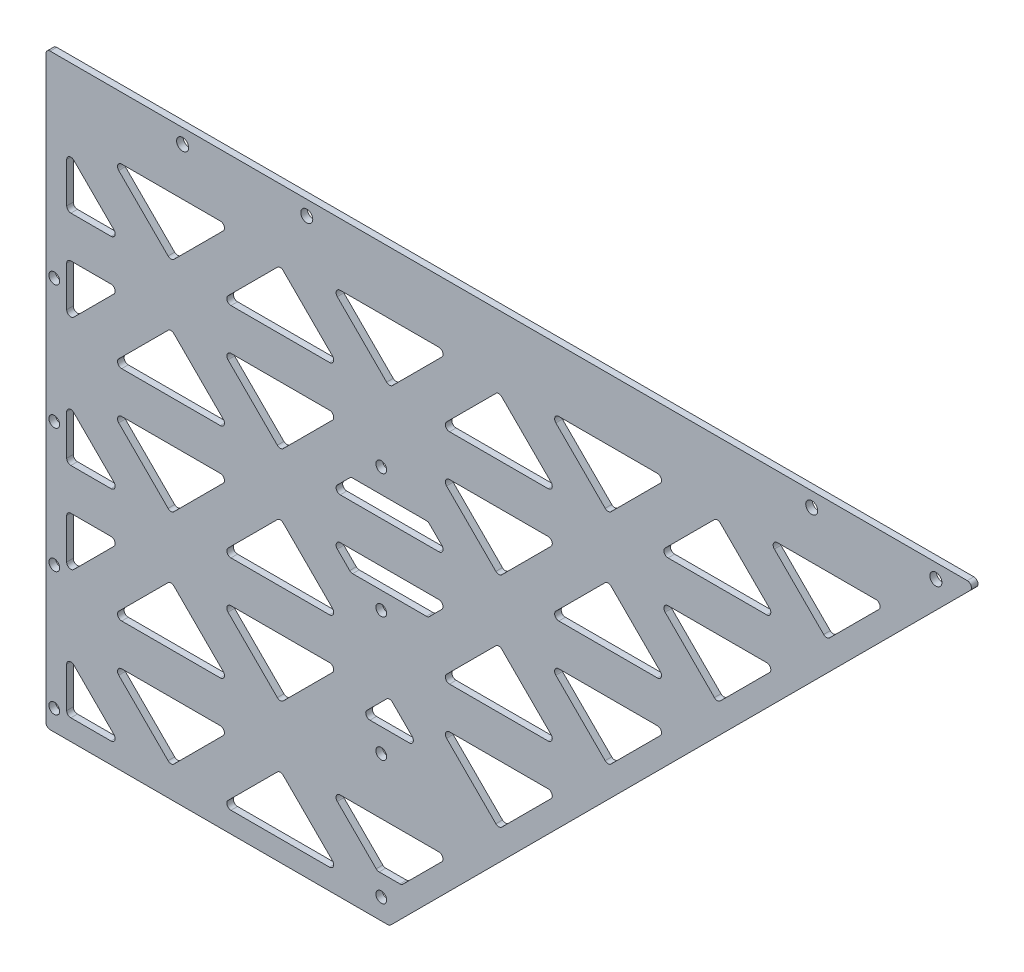
SolidWorks part; units mm, degrees
material "6061-T4 (SS)"
ref_plane "Front Plane" through (0, 0, 0) normal (0, 0, 1) x (1, 0, 0)
ref_plane "Top Plane" through (0, 0, 0) normal (0, 1, 0) x (1, 0, 0)
ref_plane "Right Plane" through (0, 0, 0) normal (1, 0, 0) x (0, 0, -1)
sketch "Sketch1" plane through (0, 0, 0) normal (0, 0, 1) x (1, 0, 0)
  line L0 (0, -71) -> (142, 71)
  line L1 (-83, 71) -> (142, 71)
  line L2 (-83, 71) -> (-83, -71)
  line L3 (-83, -71) -> (0, -71)
  line L6 (-83, 0) -> (71, 0) construction
  line L7 (0, -71) -> (0, 71) construction
  dimension "D1" = 142
  dimension "D2" = 83
  dimension "D3" = 45
extrude "Main Shape" add sketch "Sketch1" along normal mid plane 1.5875
hole_wizard "Body fasteners" positions "Sketch6" profile "Sketch7" hole size "M2" standard "ANSI Metric" end condition through all
sketch "Sketch6" plane through (0, 0, -0.7937) normal (0, 0, -1) x (-1, 0, 0)
  line L0 (81, 71) -> (81, -71) construction
  line L1 (83, 71) -> (-142, 71) construction
  line L2 (83, -71) -> (0, -71) construction
  line L4 (83, 71) -> (83, -71) construction
  line L5 (81, -66) -> (81, -36) construction
  line L6 (41.5, 71) -> (41.5, -71) construction
  line L8 (2, -66) -> (2, -36) construction
  line L9 (2, 71) -> (2, -71) construction
  point P9 (81, -66)
  point P41 (81, -36)
  point P42 (81, -6)
  point P43 (81, 24)
  point P54 (2, 24)
  point P55 (2, -6)
  point P56 (2, -36)
  point P57 (2, -66)
  dimension "D1" = 5
  dimension "D2" = 2
  dimension "D3" = 4
  dimension "D4" = 30
sketch "Sketch7" plane through (-81, -66, -0.7937) normal (1, 0, 0) x (0, 1, 0)
  line L0 (0, 0) -> (0, 1.5875)
  line L1 (0, 1.5875) -> (1.3, 1.5875)
  line L2 (1.3, 1.5875) -> (1.3, 0)
  line L5 (1.3, 0) -> (0, 0)
  line L11 (0, -6.35) -> (0, 107.95) construction
  dimension "Thru Hole Dia." = 2.6
  dimension "Thru Hole Depth" = 1.5875
hole_wizard "M2.5 Clearance Hole1" positions "Sketch11" profile "Sketch12" hole size "M2.5" standard "ANSI Metric" end condition through all
sketch "Sketch11" plane through (0, 0, 0.7937) normal (0, 0, 1) x (1, 0, 0)
  line L0 (132, 67.5) -> (132, 71) construction
  line L1 (-83, 71) -> (142, 71) construction
  line L3 (132, 67.5) -> (138.5, 67.5) construction
  line L4 (0, -71) -> (142, 71) construction
  line L6 (-83, 71) -> (-83, -71) construction
  point P0 (132, 67.5)
  point P17 (-50, 67.5)
  point P28 (-20, 67.5)
  point P31 (102, 67.5)
  dimension "D1" = 3.5
  dimension "D2" = 10
  dimension "D3" = 33
  dimension "D4" = 30
  dimension "D5" = 30
sketch "Sketch12" plane through (132, 67.5, 0.7937) normal (1, 0, 0) x (0, -1, 0)
  line L0 (0, 0) -> (0, 1.5875)
  line L1 (0, 1.5875) -> (1.45, 1.5875)
  line L2 (1.45, 1.5875) -> (1.45, 0)
  line L5 (1.45, 0) -> (0, 0)
  line L11 (0, -6.35) -> (0, 107.95) construction
  dimension "Thru Hole Dia." = 2.9
  dimension "Thru Hole Depth" = 1.5875
sketch "Sketch13" plane through (0, 0, 0.7937) normal (0, 0, 1) x (1, 0, 0)
  line L0 (-83, 61) -> (132, 61)
  line L1 (-83, 71) -> (-83, -71) construction
  line L2 (0, -71) -> (142, 71) construction
  line L3 (-83, 71) -> (142, 71) construction
  line L4 (0, -71) -> (142, 71) construction
  line L5 (0, -71) -> (0, 71) construction
  line L6 (79.2, 61) -> (105.6, 34.6)
  line L7 (105.6, 34.6) -> (52.8, 34.6)
  line L8 (52.8, 34.6) -> (79.2, 61)
  line L9 (52.8, 34.6) -> (26.4, 61)
  line L10 (26.4, 61) -> (0, 34.6)
  line L11 (0, 34.6) -> (52.8, 34.6)
  line L12 (26.4, 53.9289) -> (12.0711, 39.6)
  line L13 (38.4711, 56) -> (52.8, 41.6711)
  line L14 (12.0711, 39.6) -> (40.7289, 39.6)
  line L15 (40.7289, 39.6) -> (26.4, 53.9289)
  line L16 (79.2, 53.9289) -> (64.8711, 39.6)
  line L17 (64.8711, 39.6) -> (93.5289, 39.6)
  line L18 (93.5289, 39.6) -> (79.2, 53.9289)
  line L19 (52.8, 41.6711) -> (67.1289, 56)
  line L20 (67.1289, 56) -> (38.4711, 56)
  line L21 (-67.1289, 56) -> (-52.8, 41.6711)
  line L22 (91.2711, 56) -> (105.6, 41.6711)
  line L23 (105.6, 41.6711) -> (119.9289, 56)
  line L24 (119.9289, 56) -> (91.2711, 56)
  line L25 (0, 34.6) -> (-26.4, 61)
  line L26 (-26.4, 61) -> (-52.8, 34.6)
  line L27 (-52.8, 34.6) -> (0, 34.6)
  line L28 (-26.4, 53.9289) -> (-40.7289, 39.6)
  line L29 (-14.3289, 56) -> (0, 41.6711)
  line L30 (-40.7289, 39.6) -> (-12.0711, 39.6)
  line L31 (-12.0711, 39.6) -> (-26.4, 53.9289)
  line L32 (0, 41.6711) -> (14.3289, 56)
  line L33 (14.3289, 56) -> (-14.3289, 56)
  line L34 (52.8, 34.6) -> (0, 34.6) construction
  line L35 (-83, 61) -> (-52.8, 34.6)
  line L36 (-52.8, 34.6) -> (-83, 34.6)
  line L37 (-83, 8.2) -> (-83, 61)
  line L38 (-52.8, 41.6711) -> (-38.4711, 56)
  line L39 (-38.4711, 56) -> (-67.1289, 56)
  line L40 (-78, 52.7289) -> (-78, 39.6)
  line L41 (-78, 39.6) -> (-64.8711, 39.6)
  line L42 (-64.8711, 39.6) -> (-78, 52.7289)
  line L43 (-64.8711, 29.6) -> (-78, 16.4711)
  line L44 (-78, 29.6) -> (-64.8711, 29.6)
  line L45 (-78, 16.4711) -> (-78, 29.6)
  line L46 (-38.4711, 13.2) -> (-67.1289, 13.2)
  line L47 (-52.8, 27.5289) -> (-38.4711, 13.2)
  line L48 (-83, 8.2) -> (-52.8, 34.6)
  line L49 (14.3289, 13.2) -> (-14.3289, 13.2)
  line L51 (-12.0711, 29.6) -> (-26.4, 15.2711)
  line L52 (-40.7289, 29.6) -> (-12.0711, 29.6)
  line L54 (-26.4, 15.2711) -> (-40.7289, 29.6)
  line L55 (-26.4, 8.2) -> (-52.8, 34.6)
  line L56 (0, 34.6) -> (-26.4, 8.2)
  line L57 (-67.1289, 13.2) -> (-52.8, 27.5289)
  line L58 (40.7289, 29.6) -> (26.4, 15.2711)
  line L59 (12.0711, 29.6) -> (40.7289, 29.6)
  line L60 (38.4711, 13.2) -> (52.8, 27.5289)
  line L61 (26.4, 15.2711) -> (12.0711, 29.6)
  line L62 (26.4, 8.2) -> (0, 34.6)
  line L63 (52.8, 34.6) -> (26.4, 8.2)
  line L64 (52.8, 27.5289) -> (67.1289, 13.2)
  line L65 (67.1289, 13.2) -> (38.4711, 13.2)
  line L66 (52.8, 34.6) -> (79.2, 8.2)
  line L67 (79.2, 8.2) -> (105.6, 34.6)
  line L71 (-14.3289, 13.2) -> (-9.3289, 18.2)
  line L72 (-9.3289, 18.2) -> (9.3289, 18.2)
  line L73 (9.3289, 18.2) -> (14.3289, 13.2)
  line L74 (64.8711, 29.6) -> (93.5289, 29.6)
  line L75 (93.5289, 29.6) -> (79.2, 15.2711)
  line L76 (79.2, 15.2711) -> (64.8711, 29.6)
  line L77 (-83, 8.2) -> (79.2, 8.2)
  line L78 (26.4, 8.2) -> (52.8, -18.2)
  line L79 (52.8, -18.2) -> (79.2, 8.2)
  line L80 (26.4, 8.2) -> (0, -18.2)
  line L81 (0, -18.2) -> (52.8, -18.2)
  line L82 (9.3289, -1.8) -> (14.3289, 3.2)
  line L83 (14.3289, 3.2) -> (-14.3289, 3.2)
  line L84 (-9.3289, -1.8) -> (9.3289, -1.8)
  line L85 (-14.3289, 3.2) -> (-9.3289, -1.8)
  line L86 (-67.1289, 3.2) -> (-52.8, -11.1289)
  line L87 (-26.4, 1.1289) -> (-40.7289, -13.2)
  line L88 (-40.7289, -13.2) -> (-12.0711, -13.2)
  line L89 (-12.0711, -13.2) -> (-26.4, 1.1289)
  line L90 (-52.8, -11.1289) -> (-38.4711, 3.2)
  line L91 (-38.4711, 3.2) -> (-67.1289, 3.2)
  line L92 (-78, -0.0711) -> (-78, -13.2)
  line L93 (-78, -13.2) -> (-64.8711, -13.2)
  line L94 (-64.8711, -13.2) -> (-78, -0.0711)
  line L95 (-26.4, 8.2) -> (0, -18.2)
  line L96 (0, -18.2) -> (-83, -18.2)
  line L97 (-83, 8.2) -> (-52.8, -18.2)
  line L98 (-26.4, 8.2) -> (-52.8, -18.2)
  line L99 (52.8, -11.1289) -> (67.1289, 3.2)
  line L100 (38.4711, 3.2) -> (52.8, -11.1289)
  line L101 (67.1289, 3.2) -> (38.4711, 3.2)
  line L102 (12.0711, -13.2) -> (40.7289, -13.2)
  line L103 (26.4, 1.1289) -> (12.0711, -13.2)
  line L104 (40.7289, -13.2) -> (26.4, 1.1289)
  line L105 (26.4, -37.5289) -> (12.0711, -23.2)
  line L106 (40.7289, -23.2) -> (26.4, -37.5289)
  line L107 (12.0711, -23.2) -> (40.7289, -23.2)
  line L112 (-12.0711, -23.2) -> (-26.4, -37.5289)
  line L113 (-40.7289, -23.2) -> (-12.0711, -23.2)
  line L114 (-26.4, -37.5289) -> (-40.7289, -23.2)
  line L115 (-38.4711, -39.6) -> (-67.1289, -39.6)
  line L116 (-52.8, -25.2711) -> (-38.4711, -39.6)
  line L117 (-67.1289, -39.6) -> (-52.8, -25.2711)
  line L118 (-64.8711, -23.2) -> (-78, -36.3289)
  line L119 (-78, -23.2) -> (-64.8711, -23.2)
  line L120 (-78, -36.3289) -> (-78, -23.2)
  line L121 (-83, -44.6) -> (26.4, -44.6)
  line L122 (0, -23.2) -> (-7.1645, -30.3645)
  line L123 (-7.1645, -30.3645) -> (7.1645, -30.3645)
  line L124 (7.1645, -30.3645) -> (0, -23.2)
  line L125 (-52.8, -18.2) -> (-83, -44.6)
  line L126 (-52.8, -18.2) -> (-26.4, -44.6)
  line L127 (-26.4, -44.6) -> (0, -18.2)
  line L128 (26.4, -44.6) -> (0, -18.2)
  line L129 (-40.7289, -66) -> (-12.0711, -66)
  line L130 (-26.4, -51.6711) -> (-40.7289, -66)
  line L131 (-12.0711, -66) -> (-26.4, -51.6711)
  line L132 (-78, -66) -> (-64.8711, -66)
  line L133 (-78, -52.8711) -> (-78, -66)
  line L134 (-64.8711, -66) -> (-78, -52.8711)
  line L135 (-52.8, -63.9289) -> (-38.4711, -49.6)
  line L136 (-67.1289, -49.6) -> (-52.8, -63.9289)
  line L137 (-38.4711, -49.6) -> (-67.1289, -49.6)
  line L138 (-83, -44.6) -> (-52.8, -71)
  line L139 (-83, -71) -> (0, -71) construction
  line L140 (-52.8, -71) -> (-26.4, -44.6)
  line L141 (0, -71) -> (-26.4, -44.6)
  line L145 (2.9289, -61) -> (14.3289, -49.6)
  line L146 (14.3289, -49.6) -> (-14.3289, -49.6)
  line L147 (-2.9289, -61) -> (2.9289, -61)
  line L148 (-14.3289, -49.6) -> (-2.9289, -61)
  point P75 (11.8289, 15.7)
  point P76 (11.8289, 0.7)
  point P104 (-19.2355, -30.3645)
  dimension "D1" = 10
  dimension "D2" = 5
  dimension "D3" = 5
  dimension "D4" = 5
  dimension "D5" = 5
  dimension "D6" = 5
  dimension "D8" = 52.8
  dimension "D9" = 10
  dimension "D10" = 5
  dimension "D11" = 5
  dimension "D12" = 5
  dimension "D13" = 5
  dimension "D14" = 5
  dimension "D15" = 5
  dimension "D16" = 10
  dimension "D17" = 5
  dimension "D7" = 2
extrude "Cut-Extrude1" cut sketch "Sketch13" against normal through all both and the other way through all contours L38 L39 L21 | L30 L31 L28 | L41 L42 L40 | L32 L33 L29 | L14 L15 L12 | L17 L18 L16 | L23 L24 L22 | L19 L20 L13 | L45 L43 L44 | L57 L46 L47 | L54 L51 L52 | L73 L72 L71 L49 | L61 L58 L59 | L65 L64 L60 | L76 L75 L74 | L99 L101 L100 | L102 L104 L103 | L83 L85 L84 L82 | L88 L89 L87 | L90 L91 L86 | L93 L94 L92 | L120 L118 L119 | L117 L115 L116 | L114 L112 L113 | L123 L124 L122 | L107 L105 L106 | L146 L148 L147 L145 | L129 L131 L130 | L135 L137 L136 | L132 L134 L133 region at (26.4, 44.3763, 0.7937) region at (52.8, 51.2237, 0.7937) region at (79.2, 44.3763, 0.7937) region at (-52.8, 51.2237, 0.7937) region at (105.6, 51.2237, 0.7937) region at (-26.4, 44.3763, 0.7937) region at (0, 51.2237, 0.7937) region at (-73.6237, 43.9763, 0.7937) region at (-73.6237, 25.2237, 0.7937) region at (-52.8, 17.9763, 0.7937) region at (0, 15.5239, 0.7937) region at (-26.4, 24.8237, 0.7937) region at (26.4, 24.8237, 0.7937) region at (52.8, 17.9763, 0.7937) region at (79.2, 24.8237, 0.7937) region at (0, 0.8761, 0.7937) region at (-52.8, -1.5763, 0.7937) region at (-26.4, -8.4237, 0.7937) region at (-73.6237, -8.8237, 0.7937) region at (52.8, -1.5763, 0.7937) region at (26.4, -8.4237, 0.7937) region at (26.4, -27.9763, 0.7937) region at (-26.4, -27.9763, 0.7937) region at (-52.8, -34.8237, 0.7937) region at (-73.6237, -27.5763, 0.7937) region at (0, -27.9763, 0.7937) region at (-26.4, -61.2237, 0.7937) region at (-73.6237, -61.6237, 0.7937) region at (-52.8, -54.3763, 0.7937) region at (0, -54.0449, 0.7937)
fillet "Fillet1" radius 1 4 edges at (0, -71, 0) (-83, -71, 0) (-83, 71, 0) (142, 71, 0)
fillet "Fillet2" radius 1 93 edges at (-40.7289, -13.2, 0) (-12.0711, -13.2, 0) (-26.4, 1.1289, 0) (0, -23.2, 0) (7.1645, -30.3645, 0) (-7.1645, -30.3645, 0) (12.0711, -23.2, 0) (40.7289, -23.2, 0) (26.4, -37.5289, 0) (12.0711, -13.2, 0) (40.7289, -13.2, 0) (26.4, 1.1289, 0) (38.4711, 3.2, 0) (14.3289, 3.2, 0) (-14.3289, 3.2, 0) (9.3289, -1.8, 0) (-9.3289, -1.8, 0) (-26.4, 15.2711, 0) (-14.3289, 13.2, 0) (14.3289, 13.2, 0) (9.3289, 18.2, 0) (-12.0711, 29.6, 0) (-9.3289, 18.2, 0) (-40.7289, 29.6, 0) (-52.8, -11.1289, 0) (-67.1289, 3.2, 0) (-38.4711, 3.2, 0) (-12.0711, -23.2, 0) (-40.7289, -23.2, 0) (-26.4, -37.5289, 0) (-14.3289, -49.6, 0) (14.3289, -49.6, 0) (-2.9289, -61, 0) (2.9289, -61, 0) (-12.0711, -66, 0) (-26.4, -51.6711, 0) (-40.7289, -66, 0) (-38.4711, -39.6, 0) (-52.8, -25.2711, 0) (-67.1289, -39.6, 0) (-38.4711, -49.6, 0) (-67.1289, -49.6, 0) (-52.8, -63.9289, 0) (-64.8711, -66, 0) (-78, -66, 0) (-78, -52.8711, 0) (-64.8711, -23.2, 0) (-78, -23.2, 0) (-78, -36.3289, 0) (-78, -0.0711, 0) (-78, -13.2, 0) (-64.8711, -13.2, 0) (-67.1289, 13.2, 0) (-38.4711, 13.2, 0) (-52.8, 27.5289, 0) (-78, 16.4711, 0) (-64.8711, 29.6, 0) (-78, 29.6, 0) (-78, 39.6, 0) (-78, 52.7289, 0) (-64.8711, 39.6, 0) (-52.8, 41.6711, 0) (-38.4711, 56, 0) (-67.1289, 56, 0) (-40.7289, 39.6, 0) (-26.4, 53.9289, 0) (-12.0711, 39.6, 0) (-14.3289, 56, 0) (0, 41.6711, 0) (14.3289, 56, 0) (26.4, 53.9289, 0) (40.7289, 39.6, 0) (12.0711, 39.6, 0) (12.0711, 29.6, 0) (26.4, 15.2711, 0) (40.7289, 29.6, 0) (52.8, -11.1289, 0) (67.1289, 3.2, 0) (38.4711, 13.2, 0) (67.1289, 13.2, 0) (52.8, 27.5289, 0) (64.8711, 29.6, 0) (93.5289, 29.6, 0) (79.2, 15.2711, 0) (52.8, 41.6711, 0) (67.1289, 56, 0) (38.4711, 56, 0) (64.8711, 39.6, 0) (79.2, 53.9289, 0) (93.5289, 39.6, 0) (105.6, 41.6711, 0) (91.2711, 56, 0) (119.9289, 56, 0)
